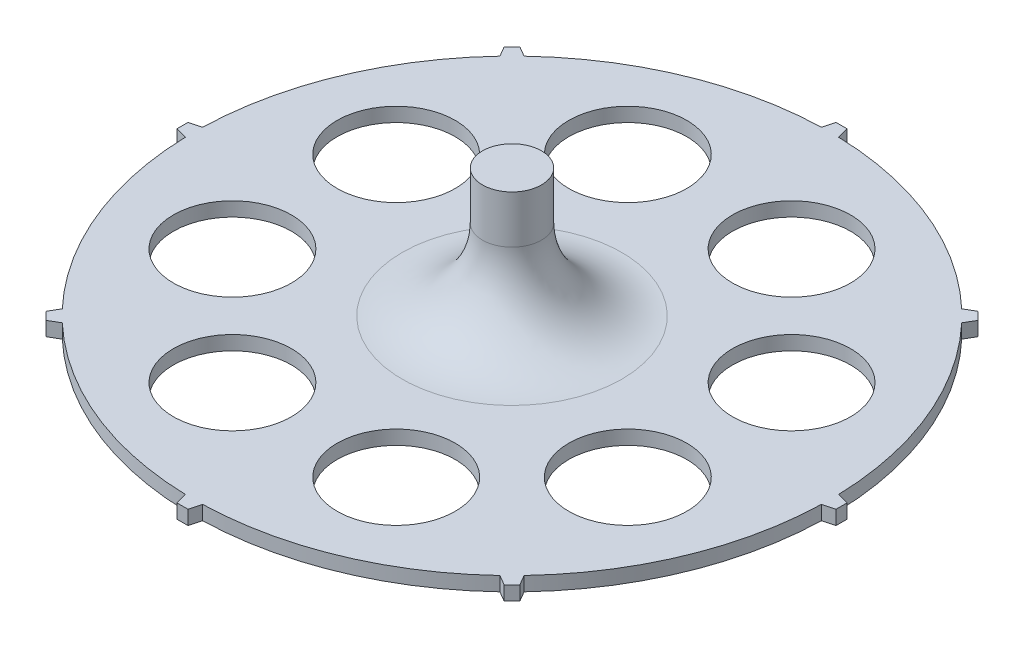
SolidWorks part; units mm, degrees
note: The reader was unsure of these and kept them because the rebuilt part matched: shared geometry of "Sketch5<5>".
ref_plane "Front Plane" through (0, 0, 0) normal (0, 0, 1) x (1, 0, 0)
ref_plane "Top Plane" through (0, 0, 0) normal (0, 1, 0) x (1, 0, 0)
ref_plane "Right Plane" through (0, 0, 0) normal (1, 0, 0) x (0, 0, -1)
sketch "Sketch1" plane through (0, 0, 0) normal (0, 1, 0) x (1, 0, 0)
  line L0 (13.6197, 91.0656) -> (13.3714, 89.4976)
  line L1 (-0.7937, 92.075) -> (0.7937, 92.075)
  line L2 (-0.7937, 92.075) -> (-0.7937, 90.4875)
  line L3 (-0.7937, 90.4875) -> (0.7937, 90.4875)
  line L4 (0.7937, 92.075) -> (0.7937, 90.4875)
  line L5 (13.6197, 91.0656) -> (15.1877, 90.8172)
  line L6 (15.1877, 90.8172) -> (14.9393, 89.2493)
  line L7 (13.3714, 89.4976) -> (14.9393, 89.2493)
  line L8 (27.6978, 87.8138) -> (27.2073, 86.304)
  line L9 (27.6978, 87.8138) -> (29.2076, 87.3232)
  line L10 (29.2076, 87.3232) -> (28.7171, 85.8134)
  line L11 (27.2073, 86.304) -> (28.7171, 85.8134)
  line L12 (41.0939, 82.3998) -> (40.3732, 80.9853)
  line L13 (41.0939, 82.3998) -> (42.5084, 81.6791)
  line L14 (42.5084, 81.6791) -> (41.7877, 80.2646)
  line L15 (40.3732, 80.9853) -> (41.7877, 80.2646)
  line L16 (53.4782, 74.9568) -> (52.5451, 73.6725)
  line L17 (53.4782, 74.9568) -> (54.7625, 74.0237)
  line L18 (54.7625, 74.0237) -> (53.8294, 72.7394)
  line L19 (52.5451, 73.6725) -> (53.8294, 72.7394)
  line L20 (64.5456, 65.6681) -> (63.4231, 64.5456)
  line L21 (64.5456, 65.6681) -> (65.6681, 64.5456)
  line L22 (65.6681, 64.5456) -> (64.5456, 63.4231)
  line L23 (63.4231, 64.5456) -> (64.5456, 63.4231)
  line L24 (74.0237, 54.7625) -> (72.7394, 53.8294)
  line L25 (74.0237, 54.7625) -> (74.9568, 53.4782)
  line L26 (74.9568, 53.4782) -> (73.6725, 52.5451)
  line L27 (72.7394, 53.8294) -> (73.6725, 52.5451)
  line L28 (81.6791, 42.5084) -> (80.2646, 41.7877)
  line L29 (81.6791, 42.5084) -> (82.3998, 41.0939)
  line L30 (82.3998, 41.0939) -> (80.9853, 40.3732)
  line L31 (80.2646, 41.7877) -> (80.9853, 40.3732)
  line L32 (87.3232, 29.2076) -> (85.8134, 28.7171)
  line L33 (87.3232, 29.2076) -> (87.8138, 27.6978)
  line L34 (87.8138, 27.6978) -> (86.304, 27.2073)
  line L35 (85.8134, 28.7171) -> (86.304, 27.2073)
  line L36 (90.8172, 15.1877) -> (89.2493, 14.9393)
  line L37 (90.8172, 15.1877) -> (91.0656, 13.6197)
  line L38 (91.0656, 13.6197) -> (89.4976, 13.3714)
  line L39 (89.2493, 14.9393) -> (89.4976, 13.3714)
  line L40 (92.075, 0.7938) -> (90.4875, 0.7938)
  line L41 (92.075, 0.7938) -> (92.075, -0.7937)
  line L42 (92.075, -0.7937) -> (90.4875, -0.7937)
  line L43 (90.4875, 0.7938) -> (90.4875, -0.7937)
  line L44 (91.0656, -13.6197) -> (89.4976, -13.3714)
  line L45 (91.0656, -13.6197) -> (90.8172, -15.1877)
  line L46 (90.8172, -15.1877) -> (89.2493, -14.9393)
  line L47 (89.4976, -13.3714) -> (89.2493, -14.9393)
  line L48 (87.8138, -27.6978) -> (86.304, -27.2073)
  line L49 (87.8138, -27.6978) -> (87.3232, -29.2076)
  line L50 (87.3232, -29.2076) -> (85.8134, -28.7171)
  line L51 (86.304, -27.2073) -> (85.8134, -28.7171)
  line L52 (82.3998, -41.0939) -> (80.9853, -40.3732)
  line L53 (82.3998, -41.0939) -> (81.6791, -42.5084)
  line L54 (81.6791, -42.5084) -> (80.2646, -41.7877)
  line L55 (80.9853, -40.3732) -> (80.2646, -41.7877)
  line L56 (74.9568, -53.4782) -> (73.6725, -52.5451)
  line L57 (74.9568, -53.4782) -> (74.0237, -54.7625)
  line L58 (74.0237, -54.7625) -> (72.7394, -53.8294)
  line L59 (73.6725, -52.5451) -> (72.7394, -53.8294)
  line L60 (65.6681, -64.5456) -> (64.5456, -63.4231)
  line L61 (65.6681, -64.5456) -> (64.5456, -65.6681)
  line L62 (64.5456, -65.6681) -> (63.4231, -64.5456)
  line L63 (64.5456, -63.4231) -> (63.4231, -64.5456)
  line L64 (54.7625, -74.0237) -> (53.8294, -72.7394)
  line L65 (54.7625, -74.0237) -> (53.4782, -74.9568)
  line L66 (53.4782, -74.9568) -> (52.5451, -73.6725)
  line L67 (53.8294, -72.7394) -> (52.5451, -73.6725)
  line L68 (42.5084, -81.6791) -> (41.7877, -80.2646)
  line L69 (42.5084, -81.6791) -> (41.0939, -82.3998)
  line L70 (41.0939, -82.3998) -> (40.3732, -80.9853)
  line L71 (41.7877, -80.2646) -> (40.3732, -80.9853)
  line L72 (29.2076, -87.3232) -> (28.7171, -85.8134)
  line L73 (29.2076, -87.3232) -> (27.6978, -87.8138)
  line L74 (27.6978, -87.8138) -> (27.2073, -86.304)
  line L75 (28.7171, -85.8134) -> (27.2073, -86.304)
  line L76 (15.1877, -90.8172) -> (14.9393, -89.2493)
  line L77 (15.1877, -90.8172) -> (13.6197, -91.0656)
  line L78 (13.6197, -91.0656) -> (13.3714, -89.4976)
  line L79 (14.9393, -89.2493) -> (13.3714, -89.4976)
  line L80 (0.7938, -92.075) -> (0.7938, -90.4875)
  line L81 (0.7938, -92.075) -> (-0.7937, -92.075)
  line L82 (-0.7937, -92.075) -> (-0.7937, -90.4875)
  line L83 (0.7938, -90.4875) -> (-0.7937, -90.4875)
  line L84 (-13.6197, -91.0656) -> (-13.3714, -89.4976)
  line L85 (-13.6197, -91.0656) -> (-15.1877, -90.8172)
  line L86 (-15.1877, -90.8172) -> (-14.9393, -89.2493)
  line L87 (-13.3714, -89.4976) -> (-14.9393, -89.2493)
  line L88 (-27.6978, -87.8138) -> (-27.2073, -86.304)
  line L89 (-27.6978, -87.8138) -> (-29.2076, -87.3232)
  line L90 (-29.2076, -87.3232) -> (-28.7171, -85.8134)
  line L91 (-27.2073, -86.304) -> (-28.7171, -85.8134)
  line L92 (-41.0939, -82.3998) -> (-40.3732, -80.9853)
  line L93 (-41.0939, -82.3998) -> (-42.5084, -81.6791)
  line L94 (-42.5084, -81.6791) -> (-41.7877, -80.2646)
  line L95 (-40.3732, -80.9853) -> (-41.7877, -80.2646)
  line L96 (-53.4782, -74.9568) -> (-52.5451, -73.6725)
  line L97 (-53.4782, -74.9568) -> (-54.7625, -74.0237)
  line L98 (-54.7625, -74.0237) -> (-53.8294, -72.7394)
  line L99 (-52.5451, -73.6725) -> (-53.8294, -72.7394)
  line L100 (-64.5456, -65.6681) -> (-63.4231, -64.5456)
  line L101 (-64.5456, -65.6681) -> (-65.6681, -64.5456)
  line L102 (-65.6681, -64.5456) -> (-64.5456, -63.4231)
  line L103 (-63.4231, -64.5456) -> (-64.5456, -63.4231)
  line L104 (-74.0237, -54.7625) -> (-72.7394, -53.8294)
  line L105 (-74.0237, -54.7625) -> (-74.9568, -53.4782)
  line L106 (-74.9568, -53.4782) -> (-73.6725, -52.5451)
  line L107 (-72.7394, -53.8294) -> (-73.6725, -52.5451)
  line L108 (-81.6791, -42.5084) -> (-80.2646, -41.7877)
  line L109 (-81.6791, -42.5084) -> (-82.3998, -41.0939)
  line L110 (-82.3998, -41.0939) -> (-80.9853, -40.3732)
  line L111 (-80.2646, -41.7877) -> (-80.9853, -40.3732)
  line L112 (-87.3232, -29.2076) -> (-85.8134, -28.7171)
  line L113 (-87.3232, -29.2076) -> (-87.8138, -27.6978)
  line L114 (-87.8138, -27.6978) -> (-86.304, -27.2073)
  line L115 (-85.8134, -28.7171) -> (-86.304, -27.2073)
  line L116 (-90.8172, -15.1877) -> (-89.2493, -14.9393)
  line L117 (-90.8172, -15.1877) -> (-91.0656, -13.6197)
  line L118 (-91.0656, -13.6197) -> (-89.4976, -13.3714)
  line L119 (-89.2493, -14.9393) -> (-89.4976, -13.3714)
  line L120 (-92.075, -0.7938) -> (-90.4875, -0.7938)
  line L121 (-92.075, -0.7938) -> (-92.075, 0.7937)
  line L122 (-92.075, 0.7937) -> (-90.4875, 0.7937)
  line L123 (-90.4875, -0.7938) -> (-90.4875, 0.7937)
  line L124 (-91.0656, 13.6197) -> (-89.4976, 13.3714)
  line L125 (-91.0656, 13.6197) -> (-90.8172, 15.1877)
  line L126 (-90.8172, 15.1877) -> (-89.2493, 14.9393)
  line L127 (-89.4976, 13.3714) -> (-89.2493, 14.9393)
  line L128 (-87.8138, 27.6978) -> (-86.304, 27.2073)
  line L129 (-87.8138, 27.6978) -> (-87.3232, 29.2076)
  line L130 (-87.3232, 29.2076) -> (-85.8134, 28.7171)
  line L131 (-86.304, 27.2073) -> (-85.8134, 28.7171)
  line L132 (-82.3998, 41.0939) -> (-80.9853, 40.3732)
  line L133 (-82.3998, 41.0939) -> (-81.6791, 42.5084)
  line L134 (-81.6791, 42.5084) -> (-80.2646, 41.7877)
  line L135 (-80.9853, 40.3732) -> (-80.2646, 41.7877)
  line L136 (-74.9568, 53.4782) -> (-73.6725, 52.5451)
  line L137 (-74.9568, 53.4782) -> (-74.0237, 54.7625)
  line L138 (-74.0237, 54.7625) -> (-72.7394, 53.8294)
  line L139 (-73.6725, 52.5451) -> (-72.7394, 53.8294)
  line L140 (-65.6681, 64.5456) -> (-64.5456, 63.4231)
  line L141 (-65.6681, 64.5456) -> (-64.5456, 65.6681)
  line L142 (-64.5456, 65.6681) -> (-63.4231, 64.5456)
  line L143 (-64.5456, 63.4231) -> (-63.4231, 64.5456)
  line L144 (-54.7625, 74.0237) -> (-53.8294, 72.7394)
  line L145 (-54.7625, 74.0237) -> (-53.4782, 74.9568)
  line L146 (-53.4782, 74.9568) -> (-52.5451, 73.6725)
  line L147 (-53.8294, 72.7394) -> (-52.5451, 73.6725)
  line L148 (-42.5084, 81.6791) -> (-41.7877, 80.2646)
  line L149 (-42.5084, 81.6791) -> (-41.0939, 82.3998)
  line L150 (-41.0939, 82.3998) -> (-40.3732, 80.9853)
  line L151 (-41.7877, 80.2646) -> (-40.3732, 80.9853)
  line L152 (-29.2076, 87.3232) -> (-28.7171, 85.8134)
  line L153 (-29.2076, 87.3232) -> (-27.6978, 87.8138)
  line L154 (-27.6978, 87.8138) -> (-27.2073, 86.304)
  line L155 (-28.7171, 85.8134) -> (-27.2073, 86.304)
  line L156 (-15.1877, 90.8172) -> (-14.9393, 89.2493)
  line L157 (-15.1877, 90.8172) -> (-13.6197, 91.0656)
  line L158 (-13.6197, 91.0656) -> (-13.3714, 89.4976)
  line L159 (-14.9393, 89.2493) -> (-13.3714, 89.4976)
  circle A0 centre (0, 0) radius 92.075
  circle A1 centre (0, 0) radius 85.725
  point P10 (0, 92.075)
  point P88 (0, 0)
  dimension "D1" = 184.15
  dimension "D2" = 6.35
  dimension "D3" = 1.5875
  dimension "D4" = 1.5875
  dimension "D5" = 40
extrude "Boss-Extrude1" add sketch "Sketch1" along normal mid plane 125.73 contours L40 A0 L38 L39 L36 L34 L35 L32 L30 L31 L28 L26 L27 L24 L22 L23 L20 L18 L19 L16 L14 L15 L12 L10 L11 L8 L6 L7 L0 L4 L3 L2 L78 L79 L76 L74 L75 L72 L70
sketch "Sketch2" plane through (0, 0, 0) normal (0, 0, 1) x (1, 0, 0)
  line L0 (0, 81.915) -> (0, 41.115)
  line L1 (0, 41.115) -> (-85.725, 41.115)
  line L2 (-85.725, 41.115) -> (-85.725, 47.465)
  line L3 (-85.725, 47.465) -> (-7.9375, 47.465)
  line L4 (-7.9375, 47.465) -> (-7.9375, 81.915)
  line L5 (-7.9375, 81.915) -> (0, 81.915)
  line L6 (90.8139, 62.865) -> (87.8106, 62.865) construction
  line L7 (92.0716, 62.865) -> (91.0622, 62.865) construction
  dimension "D1" = 6.35
  dimension "D2" = 15.4
  dimension "D3" = 19.05
  dimension "D4" = 7.9375
revolve "Revolve1" add sketch "Sketch2" angle 360 about L0
fillet "Fillet1" radius 3.175 1 edges at (85.725, 41.115, 0)
mirror "Mirror1" about plane through (0, 0, 0) normal (0, 1, 0) of "Fillet1", "Revolve1"
fillet "Fillet2" radius 21.59 2 edges at (-7.9375, -47.465, 0) (-7.9375, 47.465, 0)
sketch "Sketch3" plane through (0, 62.865, 0) normal (0, 1, 0) x (1, 0, 0)
  line L0 (-81.28, 0) -> (-90.4875, 0) construction
  line L1 (-90.4875, -0.7938) -> (-90.4875, 0.7937) construction
  line L2 (-85.6403, 3.8091) -> (-85.725, 0)
  line L3 (-85.3368, 8.1487) -> (-80.912, 7.7262)
  line L4 (-85.725, 0) -> (-81.28, 0)
  line L5 (-85.6403, 3.8091) -> (-80.9248, 7.5905)
  line L6 (-84.8905, 11.9324) -> (-79.8368, 15.2485)
  line L7 (-84.8905, 11.9324) -> (-85.3368, 8.1487)
  line L8 (-84.1758, 16.2236) -> (-79.8112, 15.3823)
  line L9 (-83.3718, 19.9478) -> (-78.0259, 22.7685)
  line L10 (-83.3718, 19.9478) -> (-84.1758, 16.2236)
  line L11 (-82.2525, 24.1515) -> (-77.9876, 22.8992)
  line L12 (-81.0982, 27.7824) -> (-75.5083, 30.0822)
  line L13 (-81.0982, 27.7824) -> (-82.2525, 24.1515)
  line L14 (-79.5843, 31.8608) -> (-75.4577, 30.2087)
  line L15 (-78.0901, 35.3655) -> (-72.3069, 37.1235)
  line L16 (-78.0901, 35.3655) -> (-79.5843, 31.8608)
  line L17 (-76.1954, 39.2815) -> (-72.2445, 37.2447)
  line L18 (-74.3748, 42.6283) -> (-68.4506, 43.8286)
  line L19 (-74.3748, 42.6283) -> (-76.1954, 39.2815)
  line L20 (-72.1165, 46.3464) -> (-68.3771, 43.9433)
  line L21 (-69.9859, 49.505) -> (-63.9745, 50.1368)
  line L22 (-69.9859, 49.505) -> (-72.1165, 46.3464)
  line L23 (-67.3844, 52.9917) -> (-63.8904, 50.244)
  line L24 (-64.9632, 55.9335) -> (-58.919, 55.9909)
  line L25 (-64.9632, 55.9335) -> (-67.3844, 52.9917)
  line L26 (-62.0421, 59.157) -> (-58.8251, 56.0896)
  line L27 (-59.3523, 61.8553) -> (-53.33, 61.338)
  line L28 (-59.3523, 61.8553) -> (-62.0421, 59.157)
  line L29 (-56.1379, 64.7866) -> (-53.2271, 61.4273)
  line L30 (-53.2038, 67.217) -> (-47.2579, 66.1296)
  line L31 (-53.2038, 67.217) -> (-56.1379, 64.7866)
  line L32 (-49.7254, 69.8295) -> (-47.147, 66.2087)
  line L33 (-46.5735, 71.97) -> (-40.7579, 70.3223)
  line L34 (-46.5735, 71.97) -> (-49.7254, 69.8295)
  line L35 (-42.8625, 74.24) -> (-40.64, 70.3905)
  line L36 (-39.5214, 76.0712) -> (-33.8888, 73.8782)
  line L37 (-39.5214, 76.0712) -> (-42.8625, 74.24)
  line L38 (-35.6115, 77.9782) -> (-33.7649, 73.9349)
  line L39 (-32.1114, 79.4835) -> (-26.7128, 76.765)
  line L40 (-32.1114, 79.4835) -> (-35.6115, 77.9782)
  line L41 (-28.0379, 81.0102) -> (-26.5841, 76.8097)
  line L42 (-24.4106, 82.176) -> (-19.2949, 78.9566)
  line L43 (-24.4106, 82.176) -> (-28.0379, 81.0102)
  line L44 (-20.2104, 83.3085) -> (-19.1625, 78.9888)
  line L45 (-16.4888, 84.1243) -> (-11.7022, 80.4332)
  line L46 (-16.4888, 84.1243) -> (-20.2104, 83.3085)
  line L47 (-12.1999, 84.8524) -> (-11.5674, 80.4527)
  line L48 (-8.4176, 85.3107) -> (-4.0035, 81.1813)
  line L49 (-8.4176, 85.3107) -> (-12.1999, 84.8524)
  line L50 (-4.079, 85.6279) -> (-3.8675, 81.1879)
  line L51 (-0.2702, 85.7246) -> (3.7314, 81.1943)
  line L52 (-0.2702, 85.7246) -> (-4.079, 85.6279)
  line L53 (4.079, 85.6279) -> (3.8675, 81.1879)
  line L54 (7.8797, 85.3621) -> (11.4325, 80.472)
  line L55 (7.8797, 85.3621) -> (4.079, 85.6279)
  line L56 (12.1999, 84.8524) -> (11.5674, 80.4527)
  line L57 (15.9582, 84.2266) -> (19.0301, 79.0209)
  line L58 (15.9582, 84.2266) -> (12.1999, 84.8524)
  line L59 (20.2104, 83.3085) -> (19.1625, 78.9888)
  line L60 (23.8922, 82.3282) -> (26.4553, 76.8541)
  line L61 (23.8922, 82.3282) -> (20.2104, 83.3085)
  line L62 (28.0379, 81.0102) -> (26.5841, 76.8097)
  line L63 (31.6098, 79.6844) -> (33.641, 73.9914)
  line L64 (31.6098, 79.6844) -> (28.0379, 81.0102)
  line L65 (35.6115, 77.9782) -> (33.7649, 73.9349)
  line L66 (39.0411, 76.3188) -> (40.522, 70.4586)
  line L67 (39.0411, 76.3188) -> (35.6115, 77.9782)
  line L68 (42.8625, 74.24) -> (40.64, 70.3905)
  line L69 (46.1189, 72.2622) -> (47.036, 66.2877)
  line L70 (46.1189, 72.2622) -> (42.8625, 74.24)
  line L71 (49.7254, 69.8295) -> (47.147, 66.2087)
  line L72 (52.779, 67.5511) -> (53.124, 61.5165)
  line L73 (52.779, 67.5511) -> (49.7254, 69.8295)
  line L74 (56.1379, 64.7866) -> (53.2271, 61.4273)
  line L75 (58.9612, 62.2282) -> (58.731, 56.1881)
  line L76 (58.9612, 62.2282) -> (56.1379, 64.7866)
  line L77 (62.0421, 59.157) -> (58.8251, 56.0896)
  line L78 (64.6094, 56.3419) -> (63.8061, 50.351)
  line L79 (64.6094, 56.3419) -> (62.0421, 59.157)
  line L80 (67.3844, 52.9917) -> (63.8904, 50.244)
  line L81 (69.6725, 49.9452) -> (68.3033, 44.0578)
  line L82 (69.6725, 49.9452) -> (67.3844, 52.9917)
  line L83 (72.1165, 46.3464) -> (68.3771, 43.9433)
  line L84 (74.1046, 43.0963) -> (72.182, 37.3657)
  line L85 (74.1046, 43.0963) -> (72.1165, 46.3464)
  line L86 (76.1954, 39.2815) -> (72.2445, 37.2447)
  line L87 (77.8656, 35.857) -> (75.407, 30.3352)
  line L88 (77.8656, 35.857) -> (76.1954, 39.2815)
  line L89 (79.5843, 31.8608) -> (75.4577, 30.2087)
  line L90 (80.9214, 28.2931) -> (77.9491, 23.0299)
  line L91 (80.9214, 28.2931) -> (79.5843, 31.8608)
  line L92 (82.2525, 24.1515) -> (77.9876, 22.8992)
  line L93 (83.2444, 20.4729) -> (79.7853, 15.5161)
  line L94 (83.2444, 20.4729) -> (82.2525, 24.1515)
  line L95 (84.1758, 16.2236) -> (79.8112, 15.3823)
  line L96 (84.8136, 12.4673) -> (80.8989, 7.8618)
  line L97 (84.8136, 12.4673) -> (84.1758, 16.2236)
  line L98 (85.3368, 8.1487) -> (80.912, 7.7262)
  line L99 (85.6146, 4.3488) -> (81.2799, 0.1362)
  line L100 (85.6146, 4.3488) -> (85.3368, 8.1487)
  line L101 (85.725, 0) -> (81.28, 0)
  line L102 (85.6403, -3.8091) -> (80.9248, -7.5905)
  line L103 (85.6403, -3.8091) -> (85.725, 0)
  line L104 (85.3368, -8.1487) -> (80.912, -7.7262)
  line L105 (84.8905, -11.9324) -> (79.8368, -15.2485)
  line L106 (84.8905, -11.9324) -> (85.3368, -8.1487)
  line L107 (84.1758, -16.2236) -> (79.8112, -15.3823)
  line L108 (83.3718, -19.9478) -> (78.0259, -22.7685)
  line L109 (83.3718, -19.9478) -> (84.1758, -16.2236)
  line L110 (82.2525, -24.1515) -> (77.9876, -22.8992)
  line L111 (81.0982, -27.7824) -> (75.5083, -30.0822)
  line L112 (81.0982, -27.7824) -> (82.2525, -24.1515)
  line L113 (79.5843, -31.8608) -> (75.4577, -30.2087)
  line L114 (78.0901, -35.3655) -> (72.3069, -37.1235)
  line L115 (78.0901, -35.3655) -> (79.5843, -31.8608)
  line L116 (76.1954, -39.2815) -> (72.2445, -37.2447)
  line L117 (74.3748, -42.6283) -> (68.4506, -43.8286)
  line L118 (74.3748, -42.6283) -> (76.1954, -39.2815)
  line L119 (72.1165, -46.3464) -> (68.3771, -43.9433)
  line L120 (69.9859, -49.505) -> (63.9745, -50.1368)
  line L121 (69.9859, -49.505) -> (72.1165, -46.3464)
  line L122 (67.3844, -52.9917) -> (63.8904, -50.244)
  line L123 (64.9632, -55.9335) -> (58.919, -55.9909)
  line L124 (64.9632, -55.9335) -> (67.3844, -52.9917)
  line L125 (62.0421, -59.157) -> (58.8251, -56.0896)
  line L126 (59.3523, -61.8553) -> (53.33, -61.338)
  line L127 (59.3523, -61.8553) -> (62.0421, -59.157)
  line L128 (56.1379, -64.7866) -> (53.2271, -61.4273)
  line L129 (53.2038, -67.217) -> (47.2579, -66.1296)
  line L130 (53.2038, -67.217) -> (56.1379, -64.7866)
  line L131 (49.7254, -69.8295) -> (47.147, -66.2087)
  line L132 (46.5735, -71.97) -> (40.7579, -70.3223)
  line L133 (46.5735, -71.97) -> (49.7254, -69.8295)
  line L134 (42.8625, -74.24) -> (40.64, -70.3905)
  line L135 (39.5214, -76.0712) -> (33.8888, -73.8782)
  line L136 (39.5214, -76.0712) -> (42.8625, -74.24)
  line L137 (35.6115, -77.9782) -> (33.7649, -73.9349)
  line L138 (32.1114, -79.4835) -> (26.7128, -76.765)
  line L139 (32.1114, -79.4835) -> (35.6115, -77.9782)
  line L140 (28.0379, -81.0102) -> (26.5841, -76.8097)
  line L141 (24.4106, -82.176) -> (19.2949, -78.9566)
  line L142 (24.4106, -82.176) -> (28.0379, -81.0102)
  line L143 (20.2104, -83.3085) -> (19.1625, -78.9888)
  line L144 (16.4888, -84.1243) -> (11.7022, -80.4332)
  line L145 (16.4888, -84.1243) -> (20.2104, -83.3085)
  line L146 (12.1999, -84.8524) -> (11.5674, -80.4527)
  line L147 (8.4176, -85.3107) -> (4.0035, -81.1813)
  line L148 (8.4176, -85.3107) -> (12.1999, -84.8524)
  line L149 (4.079, -85.6279) -> (3.8675, -81.1879)
  line L150 (0.2702, -85.7246) -> (-3.7314, -81.1943)
  line L151 (0.2702, -85.7246) -> (4.079, -85.6279)
  line L152 (-4.079, -85.6279) -> (-3.8675, -81.1879)
  line L153 (-7.8797, -85.3621) -> (-11.4325, -80.472)
  line L154 (-7.8797, -85.3621) -> (-4.079, -85.6279)
  line L155 (-12.1999, -84.8524) -> (-11.5674, -80.4527)
  line L156 (-15.9582, -84.2266) -> (-19.0301, -79.0209)
  line L157 (-15.9582, -84.2266) -> (-12.1999, -84.8524)
  line L158 (-20.2104, -83.3085) -> (-19.1625, -78.9888)
  line L159 (-23.8922, -82.3282) -> (-26.4553, -76.8541)
  line L160 (-23.8922, -82.3282) -> (-20.2104, -83.3085)
  line L161 (-28.0379, -81.0102) -> (-26.5841, -76.8097)
  line L162 (-31.6098, -79.6844) -> (-33.641, -73.9914)
  line L163 (-31.6098, -79.6844) -> (-28.0379, -81.0102)
  line L164 (-35.6115, -77.9782) -> (-33.7649, -73.9349)
  line L165 (-39.0411, -76.3188) -> (-40.522, -70.4586)
  line L166 (-39.0411, -76.3188) -> (-35.6115, -77.9782)
  line L167 (-42.8625, -74.24) -> (-40.64, -70.3905)
  line L168 (-46.1189, -72.2622) -> (-47.036, -66.2877)
  line L169 (-46.1189, -72.2622) -> (-42.8625, -74.24)
  line L170 (-49.7254, -69.8295) -> (-47.147, -66.2087)
  line L171 (-52.779, -67.5511) -> (-53.124, -61.5165)
  line L172 (-52.779, -67.5511) -> (-49.7254, -69.8295)
  line L173 (-56.1379, -64.7866) -> (-53.2271, -61.4273)
  line L174 (-58.9612, -62.2282) -> (-58.731, -56.1881)
  line L175 (-58.9612, -62.2282) -> (-56.1379, -64.7866)
  line L176 (-62.0421, -59.157) -> (-58.8251, -56.0896)
  line L177 (-64.6094, -56.3419) -> (-63.8061, -50.351)
  line L178 (-64.6094, -56.3419) -> (-62.0421, -59.157)
  line L179 (-67.3844, -52.9917) -> (-63.8904, -50.244)
  line L180 (-69.6725, -49.9452) -> (-68.3033, -44.0578)
  line L181 (-69.6725, -49.9452) -> (-67.3844, -52.9917)
  line L182 (-72.1165, -46.3464) -> (-68.3771, -43.9433)
  line L183 (-74.1046, -43.0963) -> (-72.182, -37.3657)
  line L184 (-74.1046, -43.0963) -> (-72.1165, -46.3464)
  line L185 (-76.1954, -39.2815) -> (-72.2445, -37.2447)
  line L186 (-77.8656, -35.857) -> (-75.407, -30.3352)
  line L187 (-77.8656, -35.857) -> (-76.1954, -39.2815)
  line L188 (-79.5843, -31.8608) -> (-75.4577, -30.2087)
  line L189 (-80.9214, -28.2931) -> (-77.9491, -23.0299)
  line L190 (-80.9214, -28.2931) -> (-79.5843, -31.8608)
  line L191 (-82.2525, -24.1515) -> (-77.9876, -22.8992)
  line L192 (-83.2444, -20.4729) -> (-79.7853, -15.5161)
  line L193 (-83.2444, -20.4729) -> (-82.2525, -24.1515)
  line L194 (-84.1758, -16.2236) -> (-79.8112, -15.3823)
  line L195 (-84.8136, -12.4673) -> (-80.8989, -7.8618)
  line L196 (-84.8136, -12.4673) -> (-84.1758, -16.2236)
  line L197 (-85.3368, -8.1487) -> (-80.912, -7.7262)
  line L198 (-85.6146, -4.3488) -> (-81.2799, -0.1362)
  line L199 (-85.6146, -4.3488) -> (-85.3368, -8.1487)
  circle A3 centre (0, 0) radius 85.725
  circle A4 centre (0, 0) radius 81.28
  circle A6 centre (0, 0) radius 85.725 construction
  point P233 (0, 0)
  dimension "D1" = 4.445
  dimension "D2" = 3.81
  dimension "D3" = 50
  dimension "D4" = 66
extrude "Inner Teeth" [suppressed] add sketch "Sketch3" against normal up to surface (25.4 mm away)
sketch "Sketch5" plane through (0, -47.465, 0) normal (0, -1, 0) x (1, 0, 0)
  line L0 (85.6919, 2.3812) -> (88.725, 1.5875)
  line L1 (88.725, 1.5875) -> (88.725, -1.5875)
  line L2 (88.725, -1.5875) -> (85.6919, -2.3813)
  line L3 (88.725, 0) -> (0, 0) construction
  line L4 (88.725, 0) -> (85.725, 0) construction
  line L5 (62.2771, -58.9095) -> (63.8606, -61.6155)
  line L6 (63.8606, -61.6155) -> (61.6155, -63.8606)
  line L7 (61.6155, -63.8606) -> (58.9095, -62.2771)
  line L8 (62.738, -62.738) -> (0, 0) construction
  line L9 (62.738, -62.738) -> (60.6167, -60.6167) construction
  line L10 (2.3813, -85.6919) -> (1.5875, -88.725)
  line L11 (1.5875, -88.725) -> (-1.5875, -88.725)
  line L12 (-1.5875, -88.725) -> (-2.3812, -85.6919)
  line L13 (0, -88.725) -> (0, 0) construction
  line L14 (0, -88.725) -> (0, -85.725) construction
  line L15 (-58.9095, -62.2771) -> (-61.6155, -63.8606)
  line L16 (-61.6155, -63.8606) -> (-63.8606, -61.6155)
  line L17 (-63.8606, -61.6155) -> (-62.2771, -58.9095)
  line L18 (-62.738, -62.738) -> (0, 0) construction
  line L19 (-62.738, -62.738) -> (-60.6167, -60.6167) construction
  line L20 (-85.6919, -2.3813) -> (-88.725, -1.5875)
  line L21 (-88.725, -1.5875) -> (-88.725, 1.5875)
  line L22 (-88.725, 1.5875) -> (-85.6919, 2.3812)
  line L23 (-88.725, 0) -> (0, 0) construction
  line L24 (-88.725, 0) -> (-85.725, 0) construction
  line L25 (-62.2771, 58.9095) -> (-63.8606, 61.6155)
  line L26 (-63.8606, 61.6155) -> (-61.6155, 63.8606)
  line L27 (-61.6155, 63.8606) -> (-58.9095, 62.2771)
  line L28 (-62.738, 62.738) -> (0, 0) construction
  line L29 (-62.738, 62.738) -> (-60.6167, 60.6167) construction
  line L30 (-2.3813, 85.6919) -> (-1.5875, 88.725)
  line L31 (-1.5875, 88.725) -> (1.5875, 88.725)
  line L32 (1.5875, 88.725) -> (2.3812, 85.6919)
  line L33 (0, 88.725) -> (0, 0) construction
  line L34 (0, 88.725) -> (0, 85.725) construction
  line L35 (0, 0) -> (88.725, 0) construction
  line L36 (0, 0) -> (62.738, -62.738) construction
  line L37 (85.6598, 2.2584) -> (88.598, 1.4895)
  line L38 (88.598, 1.4895) -> (88.598, -1.4895)
  line L39 (88.598, -1.4895) -> (85.6598, -2.2584)
  line L40 (62.1675, -58.9737) -> (63.7015, -61.595)
  line L41 (63.7015, -61.595) -> (61.595, -63.7015)
  line L42 (61.595, -63.7015) -> (58.9737, -62.1675)
  line L43 (2.2584, -85.6598) -> (1.4895, -88.598)
  line L44 (1.4895, -88.598) -> (-1.4895, -88.598)
  line L45 (-1.4895, -88.598) -> (-2.2584, -85.6598)
  line L46 (-58.9737, -62.1675) -> (-61.595, -63.7015)
  line L47 (-61.595, -63.7015) -> (-63.7015, -61.595)
  line L48 (-63.7015, -61.595) -> (-62.1675, -58.9737)
  line L49 (-85.6598, -2.2584) -> (-88.598, -1.4895)
  line L50 (-88.598, -1.4895) -> (-88.598, 1.4895)
  line L51 (-88.598, 1.4895) -> (-85.6598, 2.2584)
  line L52 (-62.1675, 58.9737) -> (-63.7015, 61.595)
  line L53 (-63.7015, 61.595) -> (-61.595, 63.7015)
  line L54 (-61.595, 63.7015) -> (-58.9737, 62.1675)
  line L55 (-2.2584, 85.6598) -> (-1.4895, 88.598)
  line L56 (-1.4895, 88.598) -> (1.4895, 88.598)
  line L57 (1.4895, 88.598) -> (2.2584, 85.6598)
  line L58 (0, 0) -> (85.6598, -2.2584) construction
  line L59 (0, 0) -> (58.9737, -62.1675) construction
  line L60 (58.9737, 62.1675) -> (61.595, 63.7015)
  line L61 (61.595, 63.7015) -> (63.7015, 61.595)
  line L62 (63.7015, 61.595) -> (62.1675, 58.9737)
  line L63 (58.9095, 62.2771) -> (61.6155, 63.8606)
  line L64 (61.6155, 63.8606) -> (63.8606, 61.6155)
  line L65 (63.8606, 61.6155) -> (62.2771, 58.9095)
  line L66 (62.738, 62.738) -> (0, 0) construction
  line L67 (62.738, 62.738) -> (60.6167, 60.6167) construction
  circle A2 centre (0, 0) radius 85.725 construction
  circle A5 centre (0, 0) radius 92.075
  circle A6 centre (0, 0) radius 85.725
  circle A7 centre (0, 0) radius 85.725 construction
  arc A8 (-87.8106, 27.6968) -> (-90.8139, 15.1871) centre (0, 0) ccw construction
  circle M29 centre (0, 0) radius 85.725
  dimension "D1" = 3.175
  dimension "D2" = 3
  dimension "D3" = 4.7625
  dimension "D5" = 45
  dimension "D8" = 45
  dimension "D6" = 0.127
  dimension "D4" = 8
  dimension "D7" = 8
extrude "Cut-Extrude2" cut sketch "Sketch5" against normal through all from surface at 34.45 contours A5 L31 L32 L0 L1 L2 L5 L6 L7 L10 L11 L12 L15 L16 L17 L20 L21 L22 L25 L26 L27 L30 M29 | L48 L47 L46 M29 | L47 L48 L17 L16 L15 L46 M29 | L51 L50 L49 M29 | L50 L51 L22 L21 L20 L49 M29 | L54 L53 L52 M29 | L53 L54 L27 L26 L25 L52 M29 | L57 L56 L55 M29 | L56 L57 L32 L31 L30 L55 M29 | L39 L38 L37 M29 | L38 L39 L2 L1 L0 L37 M29 | L42 L41 L40 M29 | L41 L42 L7 L6 L5 L40 M29 | L45 L44 L43 M29 | L44 L45 L12 L11 L10 L43 M29 | L62 L61 L60 M29 | L65 L64 L63 L60 L61 L62 M29 starting at face at (-7.9375, -81.915, 0)
sketch "Sketch6" plane through (0, 0, 0) normal (0, 0, 1) x (1, 0, 0)
  line L0 (-85.725, 47.465) -> (-85.725, 37.94) construction
  line L1 (-85.725, 43.655) -> (85.725, 43.655)
  line L2 (-85.725, 43.655) -> (-85.725, 18.073)
  line L3 (-85.725, 18.073) -> (85.725, 18.073)
  line L4 (85.725, 43.655) -> (85.725, 18.073)
  line L5 (85.725, 37.94) -> (85.725, 47.465) construction
  line L6 (85.725, 47.465) -> (-85.725, 47.465) construction
  dimension "D1" = 3.81
extrude "Cut-Extrude3" cut sketch "Sketch6" against normal mid plane 177.8
extrude "Boss-Extrude2" add sketch "Sketch5<5>" along direction (0, 1, 0) on the side of the normal up to surface (3.81 mm away) from surface at -94.93 contours L45 L44 L43 M29 | L48 L47 L46 M29 | L51 L50 L49 M29 | L54 L53 L52 M29 | L57 L56 L55 M29 | L62 L61 L60 M29 | L39 L38 L37 M29 | L42 L41 L40 M29 starting at face at (-29.5275, 47.465, 0)
sketch "Sketch5<5>" plane through (0, -47.465, 0) normal (0, -1, 0) x (1, 0, 0) same geometry as "Sketch5"
sketch "Sketch8" plane through (0, 47.465, 0) normal (0, 1, 0) x (1, 0, 0)
  line L0 (-85.6955, -2.249) -> (-85.5036, -2.2993)
  line L1 (-85.6955, 2.249) -> (-85.5036, 2.2993)
  line L2 (-62.1862, 59.0056) -> (-62.086, 58.8343)
  line L3 (-59.0056, 62.1862) -> (-58.8343, 62.086)
  line L4 (-2.249, 85.6955) -> (-2.2993, 85.5036)
  line L5 (2.249, 85.6955) -> (2.2993, 85.5036)
  line L6 (59.0056, 62.1862) -> (58.8343, 62.086)
  line L7 (62.1862, 59.0056) -> (62.086, 58.8343)
  line L8 (85.6955, 2.249) -> (85.5036, 2.2993)
  line L9 (85.6955, -2.249) -> (85.5036, -2.2993)
  line L10 (62.1862, -59.0056) -> (62.086, -58.8343)
  line L11 (59.0056, -62.1862) -> (58.8343, -62.086)
  line L12 (2.249, -85.6955) -> (2.2993, -85.5036)
  line L13 (-2.249, -85.6955) -> (-2.2993, -85.5036)
  line L14 (-59.0056, -62.1862) -> (-58.8343, -62.086)
  line L15 (-62.1862, -59.0056) -> (-62.086, -58.8343)
  line L40 (-59.0056, 62.1862) -> (-61.595, 63.7015)
  line L41 (-59.0056, 62.1862) -> (-61.595, 63.7015)
  line L42 (-61.595, 63.7015) -> (-63.7015, 61.595)
  line L43 (-61.595, 63.7015) -> (-63.7015, 61.595)
  line L44 (-63.7015, 61.595) -> (-62.1862, 59.0056)
  line L45 (-63.7015, 61.595) -> (-62.1862, 59.0056)
  line L46 (-85.6955, 2.249) -> (-88.598, 1.4895)
  line L47 (-85.6955, 2.249) -> (-88.598, 1.4895)
  line L72 (-88.598, 1.4895) -> (-88.598, -1.4895)
  line L73 (-88.598, 1.4895) -> (-88.598, -1.4895)
  line L74 (-88.598, -1.4895) -> (-85.6955, -2.249)
  line L75 (-88.598, -1.4895) -> (-85.6955, -2.249)
  line L76 (-62.1862, -59.0056) -> (-63.7015, -61.595)
  line L77 (-62.1862, -59.0056) -> (-63.7015, -61.595)
  line L78 (-63.7015, -61.595) -> (-61.595, -63.7015)
  line L79 (-63.7015, -61.595) -> (-61.595, -63.7015)
  line L80 (-61.595, -63.7015) -> (-59.0056, -62.1862)
  line L81 (-61.595, -63.7015) -> (-59.0056, -62.1862)
  line L82 (-2.249, -85.6955) -> (-1.4895, -88.598)
  line L83 (-2.249, -85.6955) -> (-1.4895, -88.598)
  line L84 (-1.4895, -88.598) -> (1.4895, -88.598)
  line L85 (-1.4895, -88.598) -> (1.4895, -88.598)
  line L86 (1.4895, -88.598) -> (2.249, -85.6955)
  line L87 (1.4895, -88.598) -> (2.249, -85.6955)
  line L88 (59.0056, -62.1862) -> (61.595, -63.7015)
  line L89 (59.0056, -62.1862) -> (61.595, -63.7015)
  line L90 (61.595, -63.7015) -> (63.7015, -61.595)
  line L91 (61.595, -63.7015) -> (63.7015, -61.595)
  line L92 (63.7015, -61.595) -> (62.1862, -59.0056)
  line L93 (63.7015, -61.595) -> (62.1862, -59.0056)
  line L94 (85.6955, -2.249) -> (88.598, -1.4895)
  line L95 (85.6955, -2.249) -> (88.598, -1.4895)
  line L96 (88.598, -1.4895) -> (88.598, 1.4895)
  line L97 (88.598, -1.4895) -> (88.598, 1.4895)
  line L98 (88.598, 1.4895) -> (85.6955, 2.249)
  line L99 (88.598, 1.4895) -> (85.6955, 2.249)
  line L100 (62.1862, 59.0056) -> (63.7015, 61.595)
  line L101 (62.1862, 59.0056) -> (63.7015, 61.595)
  line L102 (63.7015, 61.595) -> (61.595, 63.7015)
  line L103 (63.7015, 61.595) -> (61.595, 63.7015)
  line L104 (61.595, 63.7015) -> (59.0056, 62.1862)
  line L105 (61.595, 63.7015) -> (59.0056, 62.1862)
  line L106 (2.249, 85.6955) -> (1.4895, 88.598)
  line L107 (2.249, 85.6955) -> (1.4895, 88.598)
  line L108 (1.4895, 88.598) -> (-1.4895, 88.598)
  line L109 (1.4895, 88.598) -> (-1.4895, 88.598)
  line L110 (-1.4895, 88.598) -> (-2.249, 85.6955)
  line L111 (-1.4895, 88.598) -> (-2.249, 85.6955)
  circle A0 centre (0, 0) radius 85.5345
  arc A9 (-2.249, 85.6955) -> (-59.0056, 62.1862) centre (0, 0) ccw
  arc A10 (-62.1862, 59.0056) -> (-85.6955, 2.249) centre (0, 0) ccw
  arc A11 (-62.1862, 59.0056) -> (-85.6955, 2.249) centre (0, 0) ccw
  arc A12 (-85.6955, -2.249) -> (-62.1862, -59.0056) centre (0, 0) ccw
  arc A13 (-85.6955, -2.249) -> (-62.1862, -59.0056) centre (0, 0) ccw
  arc A14 (-59.0056, -62.1862) -> (-2.249, -85.6955) centre (0, 0) ccw
  arc A15 (-59.0056, -62.1862) -> (-2.249, -85.6955) centre (0, 0) ccw
  arc A16 (2.249, -85.6955) -> (59.0056, -62.1862) centre (0, 0) ccw
  arc A17 (-2.249, 85.6955) -> (-59.0056, 62.1862) centre (0, 0) ccw
  arc A25 (2.249, -85.6955) -> (59.0056, -62.1862) centre (0, 0) ccw
  arc A26 (62.1862, -59.0056) -> (85.6955, -2.249) centre (0, 0) ccw
  arc A27 (62.1862, -59.0056) -> (85.6955, -2.249) centre (0, 0) ccw
  arc A28 (85.6955, 2.249) -> (62.1862, 59.0056) centre (0, 0) ccw
  arc A29 (85.6955, 2.249) -> (62.1862, 59.0056) centre (0, 0) ccw
  arc A30 (59.0056, 62.1862) -> (2.249, 85.6955) centre (0, 0) ccw
  arc A31 (59.0056, 62.1862) -> (2.249, 85.6955) centre (0, 0) ccw
  point P75 (0, 0)
  arc M37 (-2.249, 85.6955) -> (-59.0056, 62.1862) centre (0, 0) ccw
  arc M41 (-62.1862, 59.0056) -> (-85.6955, 2.249) centre (0, 0) ccw
  arc M45 (-85.6955, -2.249) -> (-62.1862, -59.0056) centre (0, 0) ccw
  arc M49 (-59.0056, -62.1862) -> (-2.249, -85.6955) centre (0, 0) ccw
  arc M53 (2.249, -85.6955) -> (59.0056, -62.1862) centre (0, 0) ccw
  arc M57 (62.1862, -59.0056) -> (85.6955, -2.249) centre (0, 0) ccw
  arc M61 (85.6955, 2.249) -> (62.1862, 59.0056) centre (0, 0) ccw
  arc M65 (59.0056, 62.1862) -> (2.249, 85.6955) centre (0, 0) ccw
  dimension "D2" = 0.1905
  dimension "D1" = 0
  dimension "D3" = 8
extrude "Cut-Extrude5" cut sketch "Sketch8" against normal through all contours A0 L0 L15 M45 | A0 L14 L13 M49 | A0 L12 L11 M53 | A0 L10 L9 M57 | A0 L8 L7 M61 | A0 L6 L5 M65 | A0 L4 L3 M37 | A0 L2 L1 M41
sketch "Sketch9" plane through (0, 47.465, 0) normal (0, 1, 0) x (1, 0, 0)
  line L0 (-32.7326, 79.0236) -> (0, 0) construction
  line L1 (32.7326, 79.0236) -> (11.2997, 27.2799) construction
  circle A8 centre (-22.0162, 53.1517) radius 15.875
  circle A9 centre (22.0162, 53.1517) radius 15.875
  arc A10 (-2.2993, 85.5036) -> (-58.8343, 62.086) centre (0, 0) ccw construction
  circle A11 centre (53.1517, 22.0162) radius 15.875
  circle A12 centre (53.1517, -22.0162) radius 15.875
  circle A13 centre (22.0162, -53.1517) radius 15.875
  circle A14 centre (-22.0162, -53.1517) radius 15.875
  circle A15 centre (-53.1517, -22.0162) radius 15.875
  circle A16 centre (-53.1517, 22.0162) radius 15.875
  arc A17 (58.8343, 62.086) -> (2.2993, 85.5036) centre (0, 0) ccw construction
  circle A18 centre (0, 0) radius 29.5275 construction
  point P1 (22.0162, 53.1517)
  point P21 (0, 0)
  dimension "D1" = 31.75
  dimension "D2" = 8
extrude "Cut-Extrude6" cut sketch "Sketch9" against normal through all
